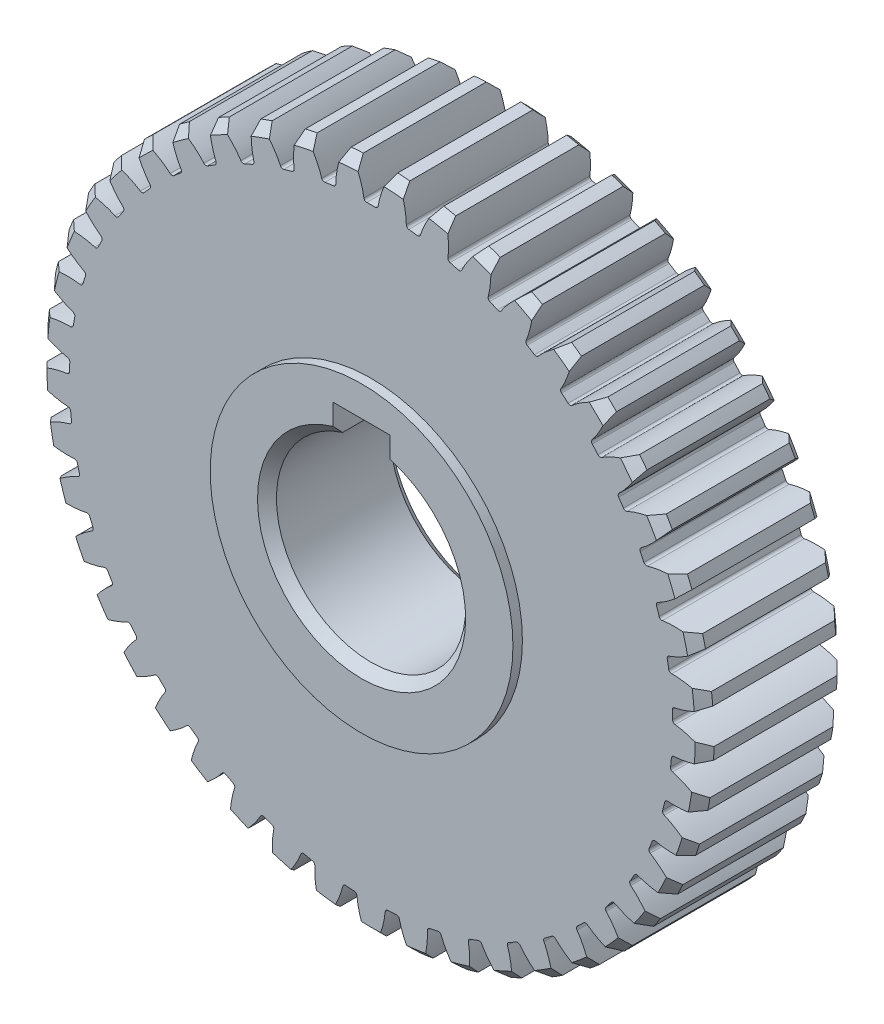
SolidWorks part; units mm, degrees
ref_plane "中间平面" through (0, 0, 0) normal (0, 0, 1) x (1, 0, 0)
ref_plane "上视基准面" through (0, 0, 0) normal (0, 1, 0) x (1, 0, 0)
ref_plane "右视基准面" through (0, 0, 0) normal (1, 0, 0) x (0, 0, -1)
sketch "直齿轮" plane through (0, 0, 0) normal (0, 0, 1) x (1, 0, 0)
  line L0 (0, 0) -> (-1.1779, 33.7294) construction
  line L2 (-0.7118, 31.7066) -> (0, 0)
  line L3 (0, 0) -> (0, 52) construction
  line L4 (1.1779, 33.7294) -> (0, 0) construction
  line L6 (0, 0) -> (0.7118, 31.7066)
  circle A0 centre (0, 0) radius 31.7146
  circle A1 centre (0, 0) radius 31.875
  arc A2 (1.1779, 33.7294) -> (-1.1779, 33.7294) centre (0, 0) ccw
  circle A3 centre (0, 0) radius 35.25
  spline S0 degree 4 poles (-0.7118, 31.7066) (-0.7131, 31.767) (-0.7195, 31.8874) (-0.7472, 32.1272) (-0.8085, 32.472) (-0.9001, 32.8601) (-1.0554, 33.3941) (-1.2518, 33.9493) (-1.4939, 34.5344) (-1.7844, 35.1466) (-2.0692, 35.6895) (-2.7, 36.7895) (-3.8251, 38.4176) (-5.8319, 40.7065) (-8.9711, 43.3563) (-12.802, 45.7416) (-17.2446, 47.7171) (-21.8947, 49.1277) (-26.6727, 50.004) (-31.7544, 50.3942) (-38.0635, 50.219) (-45.5098, 49.0466) (-53.8736, 46.4353) (-61.5126, 42.6716) (-67.6148, 38.6906) (-73.3205, 34.1727) (-77.726, 29.9963) (-81.7586, 25.4604) (-85.4024, 20.6134) (-88.0792, 16.5677) (-91.1224, 11.3231) (-94.2841, 4.7639) (-96.8263, -2.0649) (-98.5878, -8.5017) (-99.5813, -13.2481) (-100.1002, -16.2341) (-100.41, -18.3319) (-100.6375, -20.1372) (-100.8019, -21.641) (-100.9184, -22.852) (-101.0197, -24.0513) (-101.1063, -25.275) (-101.1825, -26.5453) (-101.2374, -27.7802) (-101.2725, -28.7879) (-101.2981, -29.9379) (-101.308, -30.6277) (-101.3158, -31.7348) (-101.3098, -32.6002) (-101.2971, -33.646) (-101.2732, -34.583) (-101.2408, -35.5853) (-101.1984, -36.5478) (-101.1469, -37.5332) (-101.0859, -38.5048) (-100.9981, -39.727) (-100.8741, -41.1871) (-100.7269, -42.6485) (-100.5568, -44.1049) (-100.4312, -45.0756) (-100.3654, -45.5599) (-100.3317, -45.8022) knots 0 0 0 0 0 0.001401 0.002802 0.005604 0.008133 0.010661 0.015718 0.019279 0.022839 0.026399 0.02996 0.048734 0.068727 0.096889 0.125051 0.153212 0.181374 0.209535 0.237696 0.271429 0.327752 0.384075 0.440398 0.46856 0.496721 0.553044 0.581206 0.609367 0.637529 0.66569 0.722013 0.778336 0.806497 0.820578 0.834659 0.84874 0.85578 0.86282 0.869861 0.876901 0.883942 0.890982 0.900036 0.904564 0.909091 0.914773 0.920455 0.926136 0.931818 0.9375 0.943182 0.948864 0.954545 0.960227 0.965909 0.977273 0.988636 0.994318 1 1 1 1 1 construction
  spline S1 degree 4 poles (-0.7118, 31.7066) (-0.7131, 31.767) (-0.7195, 31.8874) (-0.7472, 32.1272) (-0.8085, 32.472) (-0.9001, 32.8601) (-1.0554, 33.3941) (-1.2518, 33.9493) (-1.4939, 34.5344) (-1.7844, 35.1466) (-2.0692, 35.6895) (-2.7, 36.7895) (-3.8251, 38.4176) (-5.8319, 40.7065) (-8.9711, 43.3563) (-12.802, 45.7416) (-17.2446, 47.7171) (-21.8947, 49.1277) (-26.6727, 50.004) (-31.7544, 50.3942) (-38.0635, 50.219) (-45.5098, 49.0466) (-53.8736, 46.4353) (-61.5126, 42.6716) (-67.6148, 38.6906) (-73.3205, 34.1727) (-77.726, 29.9963) (-81.7586, 25.4604) (-85.4024, 20.6134) (-88.0792, 16.5677) (-91.1224, 11.3231) (-94.2841, 4.7639) (-96.8263, -2.0649) (-98.5878, -8.5017) (-99.5813, -13.2481) (-100.1002, -16.2341) (-100.41, -18.3319) (-100.6375, -20.1372) (-100.8019, -21.641) (-100.9184, -22.852) (-101.0197, -24.0513) (-101.1063, -25.275) (-101.1825, -26.5453) (-101.2374, -27.7802) (-101.2725, -28.7879) (-101.292, -29.6633) (-101.2984, -30.02) (-101.3011, -30.1971) knots 0 0 0 0 0 0.001401 0.002802 0.005604 0.008133 0.010661 0.015718 0.019279 0.022839 0.026399 0.02996 0.048734 0.068727 0.096889 0.125051 0.153212 0.181374 0.209535 0.237696 0.271429 0.327752 0.384075 0.440398 0.46856 0.496721 0.553044 0.581206 0.609367 0.637529 0.66569 0.722013 0.778336 0.806497 0.820578 0.834659 0.84874 0.85578 0.86282 0.869861 0.876901 0.883942 0.890982 0.900036 0.904564 0.909091 0.909091 0.909091 0.909091 0.909091
  spline S2 degree 4 poles (0.7118, 31.7066) (0.7131, 31.767) (0.7195, 31.8874) (0.7472, 32.1272) (0.8085, 32.472) (0.9001, 32.8601) (1.0554, 33.3941) (1.2518, 33.9493) (1.4939, 34.5344) (1.7844, 35.1466) (2.0692, 35.6895) (2.7, 36.7895) (3.8251, 38.4176) (5.8319, 40.7065) (8.9711, 43.3563) (12.802, 45.7416) (17.2446, 47.7171) (21.8947, 49.1277) (26.6727, 50.004) (31.7544, 50.3942) (38.0635, 50.219) (45.5098, 49.0466) (53.8736, 46.4353) (61.5126, 42.6716) (67.6148, 38.6906) (73.3205, 34.1727) (77.726, 29.9963) (81.7586, 25.4604) (85.4024, 20.6134) (88.0792, 16.5677) (91.1224, 11.3231) (94.2841, 4.7639) (96.8263, -2.0649) (98.5878, -8.5017) (99.5813, -13.2481) (100.1002, -16.2341) (100.41, -18.3319) (100.6375, -20.1372) (100.8019, -21.641) (100.9184, -22.852) (101.0197, -24.0513) (101.1063, -25.275) (101.1825, -26.5453) (101.2374, -27.7802) (101.2725, -28.7879) (101.2981, -29.9379) (101.308, -30.6277) (101.3158, -31.7348) (101.3098, -32.6002) (101.2971, -33.646) (101.2732, -34.583) (101.2408, -35.5853) (101.1984, -36.5478) (101.1469, -37.5332) (101.0859, -38.5048) (100.9981, -39.727) (100.8741, -41.1871) (100.7269, -42.6485) (100.5568, -44.1049) (100.4312, -45.0756) (100.3654, -45.5599) (100.3317, -45.8022) knots 0 0 0 0 0 0.001401 0.002802 0.005604 0.008133 0.010661 0.015718 0.019279 0.022839 0.026399 0.02996 0.048734 0.068727 0.096889 0.125051 0.153212 0.181374 0.209535 0.237696 0.271429 0.327752 0.384075 0.440398 0.46856 0.496721 0.553044 0.581206 0.609367 0.637529 0.66569 0.722013 0.778336 0.806497 0.820578 0.834659 0.84874 0.85578 0.86282 0.869861 0.876901 0.883942 0.890982 0.900036 0.904564 0.909091 0.914773 0.920455 0.926136 0.931818 0.9375 0.943182 0.948864 0.954545 0.960227 0.965909 0.977273 0.988636 0.994318 1 1 1 1 1 construction
  spline S3 degree 4 poles (0.7118, 31.7066) (0.7131, 31.767) (0.7195, 31.8874) (0.7472, 32.1272) (0.8085, 32.472) (0.9001, 32.8601) (1.0554, 33.3941) (1.2518, 33.9493) (1.4939, 34.5344) (1.7844, 35.1466) (2.0692, 35.6895) (2.7, 36.7895) (3.8251, 38.4176) (5.8319, 40.7065) (8.9711, 43.3563) (12.802, 45.7416) (17.2446, 47.7171) (21.8947, 49.1277) (26.6727, 50.004) (31.7544, 50.3942) (38.0635, 50.219) (45.5098, 49.0466) (53.8736, 46.4353) (61.5126, 42.6716) (67.6148, 38.6906) (73.3205, 34.1727) (77.726, 29.9963) (81.7586, 25.4604) (85.4024, 20.6134) (88.0792, 16.5677) (91.1224, 11.3231) (94.2841, 4.7639) (96.8263, -2.0649) (98.5878, -8.5017) (99.5813, -13.2481) (100.1002, -16.2341) (100.41, -18.3319) (100.6375, -20.1372) (100.8019, -21.641) (100.9184, -22.852) (101.0197, -24.0513) (101.1063, -25.275) (101.1825, -26.5453) (101.2374, -27.7802) (101.2725, -28.7879) (101.292, -29.6633) (101.2984, -30.02) (101.3011, -30.1971) knots 0 0 0 0 0 0.001401 0.002802 0.005604 0.008133 0.010661 0.015718 0.019279 0.022839 0.026399 0.02996 0.048734 0.068727 0.096889 0.125051 0.153212 0.181374 0.209535 0.237696 0.271429 0.327752 0.384075 0.440398 0.46856 0.496721 0.553044 0.581206 0.609367 0.637529 0.66569 0.722013 0.778336 0.806497 0.820578 0.834659 0.84874 0.85578 0.86282 0.869861 0.876901 0.883942 0.890982 0.900036 0.904564 0.909091 0.909091 0.909091 0.909091 0.909091
  dimension "基圆直径" = 63.4293
  dimension "齿根圆" = 63.75
  dimension "分度圆" = 67.5
  dimension "齿顶圆" = 70.5
  dimension "D1" = 2.3562
sketch "圆" plane through (0, 0, 0) normal (0, 0, 1) x (1, 0, 0)
  circle A0 centre (0, 0) radius 35.25 construction
  circle A1 centre (0, 0) radius 35.25
extrude "毛胚" add sketch "圆" along normal mid plane 15
chamfer "轮齿倒角" distance 1 angle 45 2 edges at (35.25, 0, -7.5) (35.25, 0, 7.5)
sketch "齿形" plane through (0, 0, 0) normal (0, 0, 1) x (1, 0, 0)
  line L4 (0, 0) -> (0.7118, 31.7066) construction
  line L5 (-0.7118, 31.7066) -> (0, 0) construction
  line L6 (0, 0) -> (0.7118, 31.7066)
  line L7 (-0.7118, 31.7066) -> (0, 0)
  circle A4 centre (0, 0) radius 31.875 construction
  circle A5 centre (0, 0) radius 35.25 construction
  circle A6 centre (0, 0) radius 31.875
  circle A7 centre (0, 0) radius 35.25
  spline S1 degree 4 poles (-998.7009, 6.59) (35.6319, 24.6138) (1.554, 27.0412) (0.3384, 29.8291) (0.8085, 32.472) (0.9001, 32.8601) (1.0554, 33.3941) (1.2518, 33.9493) (1.4939, 34.5344) (1.7844, 35.1466) (2.0692, 35.6895) (2.7, 36.7895) (3.8251, 38.4176) (5.8319, 40.7065) (8.9711, 43.3563) (12.802, 45.7416) (17.2446, 47.7171) (21.8947, 49.1277) (26.6727, 50.004) (31.7544, 50.3942) (38.0635, 50.219) (45.5098, 49.0466) (53.8736, 46.4353) (61.5126, 42.6716) (67.6148, 38.6906) (73.3205, 34.1727) (77.726, 29.9963) (81.7586, 25.4604) (85.4024, 20.6134) (88.0792, 16.5677) (91.1224, 11.3231) (94.2841, 4.7639) (96.8263, -2.0649) (98.5878, -8.5017) (99.5813, -13.2481) (100.1002, -16.2341) (100.41, -18.3319) (100.6375, -20.1372) (100.8019, -21.641) (100.9184, -22.852) (101.0197, -24.0513) (101.1063, -25.275) (101.1825, -26.5453) (101.2374, -27.7802) (101.352, -31.0658) (101.3561, -36.6373) (100.5875, 2.1715) (116.0578, -1029.7436) knots -0.054205 -0.054205 -0.054205 -0.054205 -0.054205 0.001401 0.002802 0.005604 0.008133 0.010661 0.015718 0.019279 0.022839 0.026399 0.02996 0.048734 0.068727 0.096889 0.125051 0.153212 0.181374 0.209535 0.237696 0.271429 0.327752 0.384075 0.440398 0.46856 0.496721 0.553044 0.581206 0.609367 0.637529 0.66569 0.722013 0.778336 0.806497 0.820578 0.834659 0.84874 0.85578 0.86282 0.869861 0.876901 0.883942 0.890982 0.900036 0.904564 0.965946 0.965946 0.965946 0.965946 0.965946 only from (0.7118, 31.7066) to (101.3011, -30.1971) construction
  spline S3 degree 4 poles (998.7009, 6.59) (-35.6319, 24.6138) (-1.554, 27.0412) (-0.3384, 29.8291) (-0.8085, 32.472) (-0.9001, 32.8601) (-1.0554, 33.3941) (-1.2518, 33.9493) (-1.4939, 34.5344) (-1.7844, 35.1466) (-2.0692, 35.6895) (-2.7, 36.7895) (-3.8251, 38.4176) (-5.8319, 40.7065) (-8.9711, 43.3563) (-12.802, 45.7416) (-17.2446, 47.7171) (-21.8947, 49.1277) (-26.6727, 50.004) (-31.7544, 50.3942) (-38.0635, 50.219) (-45.5098, 49.0466) (-53.8736, 46.4353) (-61.5126, 42.6716) (-67.6148, 38.6906) (-73.3205, 34.1727) (-77.726, 29.9963) (-81.7586, 25.4604) (-85.4024, 20.6134) (-88.0792, 16.5677) (-91.1224, 11.3231) (-94.2841, 4.7639) (-96.8263, -2.0649) (-98.5878, -8.5017) (-99.5813, -13.2481) (-100.1002, -16.2341) (-100.41, -18.3319) (-100.6375, -20.1372) (-100.8019, -21.641) (-100.9184, -22.852) (-101.0197, -24.0513) (-101.1063, -25.275) (-101.1825, -26.5453) (-101.2374, -27.7802) (-101.352, -31.0658) (-101.3561, -36.6373) (-100.5875, 2.1715) (-116.0578, -1029.7436) knots -0.054205 -0.054205 -0.054205 -0.054205 -0.054205 0.001401 0.002802 0.005604 0.008133 0.010661 0.015718 0.019279 0.022839 0.026399 0.02996 0.048734 0.068727 0.096889 0.125051 0.153212 0.181374 0.209535 0.237696 0.271429 0.327752 0.384075 0.440398 0.46856 0.496721 0.553044 0.581206 0.609367 0.637529 0.66569 0.722013 0.778336 0.806497 0.820578 0.834659 0.84874 0.85578 0.86282 0.869861 0.876901 0.883942 0.890982 0.900036 0.904564 0.965946 0.965946 0.965946 0.965946 0.965946 only from (-0.7118, 31.7066) to (-101.3011, -30.1971) construction
  spline S4 degree 4 poles (0.7118, 31.7066) (0.7131, 31.767) (0.7195, 31.8874) (0.7472, 32.1272) (0.8085, 32.472) (0.9001, 32.8601) (1.0554, 33.3941) (1.2518, 33.9493) (1.4939, 34.5344) (1.7844, 35.1466) (2.0692, 35.6895) (2.7, 36.7895) (3.8251, 38.4176) (5.8319, 40.7065) (8.9711, 43.3563) (12.802, 45.7416) (17.2446, 47.7171) (21.8947, 49.1277) (26.6727, 50.004) (31.7544, 50.3942) (38.0635, 50.219) (45.5098, 49.0466) (53.8736, 46.4353) (61.5126, 42.6716) (67.6148, 38.6906) (73.3205, 34.1727) (77.726, 29.9963) (81.7586, 25.4604) (85.4024, 20.6134) (88.0792, 16.5677) (91.1224, 11.3231) (94.2841, 4.7639) (96.8263, -2.0649) (98.5878, -8.5017) (99.5813, -13.2481) (100.1002, -16.2341) (100.41, -18.3319) (100.6375, -20.1372) (100.8019, -21.641) (100.9184, -22.852) (101.0197, -24.0513) (101.1063, -25.275) (101.1825, -26.5453) (101.2374, -27.7802) (101.2725, -28.7879) (101.292, -29.6633) (101.2984, -30.02) (101.3011, -30.1971) knots 0 0 0 0 0 0.001401 0.002802 0.005604 0.008133 0.010661 0.015718 0.019279 0.022839 0.026399 0.02996 0.048734 0.068727 0.096889 0.125051 0.153212 0.181374 0.209535 0.237696 0.271429 0.327752 0.384075 0.440398 0.46856 0.496721 0.553044 0.581206 0.609367 0.637529 0.66569 0.722013 0.778336 0.806497 0.820578 0.834659 0.84874 0.85578 0.86282 0.869861 0.876901 0.883942 0.890982 0.900036 0.904564 0.909091 0.909091 0.909091 0.909091 0.909091
  spline S5 degree 4 poles (-0.7118, 31.7066) (-0.7131, 31.767) (-0.7195, 31.8874) (-0.7472, 32.1272) (-0.8085, 32.472) (-0.9001, 32.8601) (-1.0554, 33.3941) (-1.2518, 33.9493) (-1.4939, 34.5344) (-1.7844, 35.1466) (-2.0692, 35.6895) (-2.7, 36.7895) (-3.8251, 38.4176) (-5.8319, 40.7065) (-8.9711, 43.3563) (-12.802, 45.7416) (-17.2446, 47.7171) (-21.8947, 49.1277) (-26.6727, 50.004) (-31.7544, 50.3942) (-38.0635, 50.219) (-45.5098, 49.0466) (-53.8736, 46.4353) (-61.5126, 42.6716) (-67.6148, 38.6906) (-73.3205, 34.1727) (-77.726, 29.9963) (-81.7586, 25.4604) (-85.4024, 20.6134) (-88.0792, 16.5677) (-91.1224, 11.3231) (-94.2841, 4.7639) (-96.8263, -2.0649) (-98.5878, -8.5017) (-99.5813, -13.2481) (-100.1002, -16.2341) (-100.41, -18.3319) (-100.6375, -20.1372) (-100.8019, -21.641) (-100.9184, -22.852) (-101.0197, -24.0513) (-101.1063, -25.275) (-101.1825, -26.5453) (-101.2374, -27.7802) (-101.2725, -28.7879) (-101.292, -29.6633) (-101.2984, -30.02) (-101.3011, -30.1971) knots 0 0 0 0 0 0.001401 0.002802 0.005604 0.008133 0.010661 0.015718 0.019279 0.022839 0.026399 0.02996 0.048734 0.068727 0.096889 0.125051 0.153212 0.181374 0.209535 0.237696 0.271429 0.327752 0.384075 0.440398 0.46856 0.496721 0.553044 0.581206 0.609367 0.637529 0.66569 0.722013 0.778336 0.806497 0.820578 0.834659 0.84874 0.85578 0.86282 0.869861 0.876901 0.883942 0.890982 0.900036 0.904564 0.909091 0.909091 0.909091 0.909091 0.909091
extrude "插齿" cut sketch "齿形" against normal mid plane 15 contours S5 A6 S4 A7
fillet "圆角1" radius 0.3 2 edges at (0.7202, 31.8669, 0) (-0.7202, 31.8669, 0)
pattern_circular "圆周阵列1" count 45 over 360 about axis through (0, 0, 7.5) along (0, 0, -1) of "插齿", "圆角1"
fillet "圆角2" [suppressed] radius 0.3
pattern_circular "圆周阵列2" [suppressed] count 45 over 360
sketch "分度圆" plane through (0, 0, 0) normal (0, 0, 1) x (1, 0, 0)
  circle A0 centre (0, 0) radius 33.75 construction
  circle A1 centre (0, 0) radius 33.75 construction
sketch "草图1" plane through (0, 0, 7.5) normal (0, 0, 1) x (1, 0, 0)
  circle A0 centre (0, 0) radius 16
  dimension "D1" = 32
extrude "凸台-拉伸1" add sketch "草图1" along normal blind 1
sketch "草图2" plane through (0, 0, -7.5) normal (0, 0, -1) x (-1, 0, 0)
  circle A0 centre (0, 0) radius 20
  dimension "D1" = 40
extrude "切除-拉伸1" cut sketch "草图2" against normal blind 2 and the other way through all
sketch "草图3" plane through (0, 0, -5.5) normal (0, 0, -1) x (-1, 0, 0)
  line L0 (3, 7.2) -> (3, 9.5394) construction
  line L1 (-3, 7.2) -> (3, 7.2) construction
  line L2 (-3, 9.5394) -> (-3, 12.8)
  line L3 (-3, 12.8) -> (3, 12.8)
  line L4 (3, 9.5394) -> (3, 12.8)
  line L5 (0, 10) -> (3, 12.8) construction
  line L6 (-3, 12.8) -> (0, 10) construction
  line L7 (0, 10) -> (3, 7.2) construction
  line L8 (-3, 7.2) -> (0, 10) construction
  line L9 (-3, 7.2) -> (-3, 9.5394) construction
  arc A0 (-3, 9.5394) -> (3, 9.5394) centre (0, 0) ccw
  arc A1 (0, 10) -> (-3, 9.5394) centre (0, 0) ccw construction
  arc A2 (3, 9.5394) -> (0, 10) centre (0, 0) ccw construction
  point P3 (0, 10)
  dimension "D1" = 20
  dimension "D2" = 22.8
  dimension "D3" = 6
extrude "切除-拉伸2" cut sketch "草图3" against normal through all
chamfer "倒角1" distance 1 angle 45 2 edges at (0, -10, -5.5) (0, -10, 8.5)
equation "\"m\" = 1.5'模数"
equation "\"z\" = 45'齿数"
equation "\"a\"= 20'压力角（常见为20°）"
equation "\"B\" = 15'齿宽"
equation "\"C1\"= 1'轮齿倒角（若设为0，则无倒角）"
equation "\"x\"= 0'变位系数（不懂勿动）"
equation "\"ha\"= 1'齿顶高系数（不懂勿动）"
equation "\"c\"= 0.25'顶隙系数（不懂勿动）"
equation "\"基圆直径@直齿轮\"= \"m\" * \"z\" * cos ( \"a\" )"
equation "\"齿根圆@直齿轮\" = \"m\" * ( \"z\" - 2 * ( \"ha\" - \"x\" + \"c\" ) )"
equation "\"分度圆@直齿轮\"=\"m\" * \"z\""
equation "\"齿顶圆@直齿轮\" = \"m\" * ( \"z\" + 2 * ( \"ha\" + \"x\" ) )"
equation "\"R\"= 0.3'齿根圆角"
equation "\"D1\"= \"R\""
equation "\"D1@毛胚\" = \"B\""
equation "\"D1@轮齿倒角\" = IIF ( \"C1\" > 0 , \"C1\" , 0.001 )"
equation "\"轮齿倒角\"= IIF ( \"C1\" > 0 , \"unsuppressed\" , \"suppressed\" )"
equation "\"D1@插齿\" = \"B\""
equation "\"D1@圆周阵列1\" = \"z\""
equation "\"D1@直齿轮\"= \"m\" * ( pi / 2 ) - 2 * \"m\" * tan ( \"a\" ) * \"x\"'作者：机械菌-"
equation "\"D1@圆角1\"=\"R\""
equation "\"圆角1\" = IIF ( \"m\" * ( \"z\" - 2 * ( \"ha\" - \"x\" + \"c\" ) ) > \"m\" * \"z\" * cos ( \"a\" ) , \"unsuppressed\" , \"suppressed\" )"
equation "\"圆周阵列1\"= IIF ( \"m\" * ( \"z\" - 2 * ( \"ha\" - \"x\" + \"c\" ) ) > \"m\" * \"z\" * cos ( \"a\" ) , \"unsuppressed\" , \"suppressed\" )"
equation "\"D1@圆角2\"=\"R\""
equation "\"D1@圆周阵列2\" = \"z\""
equation "\"圆角2\" = IIF ( \"m\" * ( \"z\" - 2 * ( \"ha\" - \"x\" + \"c\" ) ) < \"m\" * \"z\" * cos ( \"a\" ) , \"unsuppressed\" , \"suppressed\" )"
equation "\"圆周阵列2\"= IIF ( \"m\" *  ( \"z\" - 2 *  ( \"ha\" - \"x\" + \"c\" )  )  < \"m\" * \"z\" * cos ( \"a\" )  ,  unsuppressed  ,  suppressed  ) "
